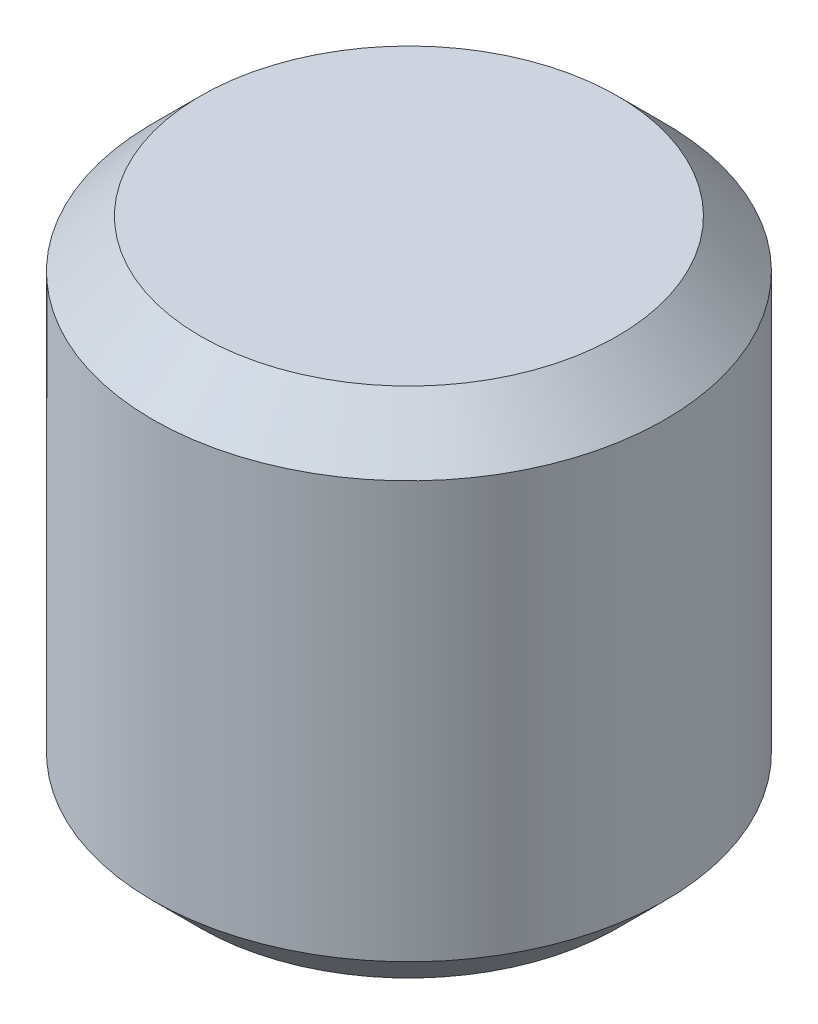
SolidWorks part; units mm, degrees
ref_plane "Front Plane" through (0, 0, 0) normal (0, 0, 1) x (1, 0, 0)
ref_plane "Top Plane" through (0, 0, 0) normal (0, 1, 0) x (1, 0, 0)
ref_plane "Right Plane" through (0, 0, 0) normal (1, 0, 0) x (0, 0, -1)
sketch "Sketch1" plane through (0, 0, 0) normal (0, 1, 0) x (1, 0, 0)
  circle A0 centre (0, 0) radius 6.35
  dimension "D1" = 12.7
extrude "Boss-Extrude1" add sketch "Sketch1" along normal blind 12.7
chamfer "Chamfer1" distance 1.1906 angle 45 2 edges at (0, 0, 6.35) (0, 12.7, 6.35)
